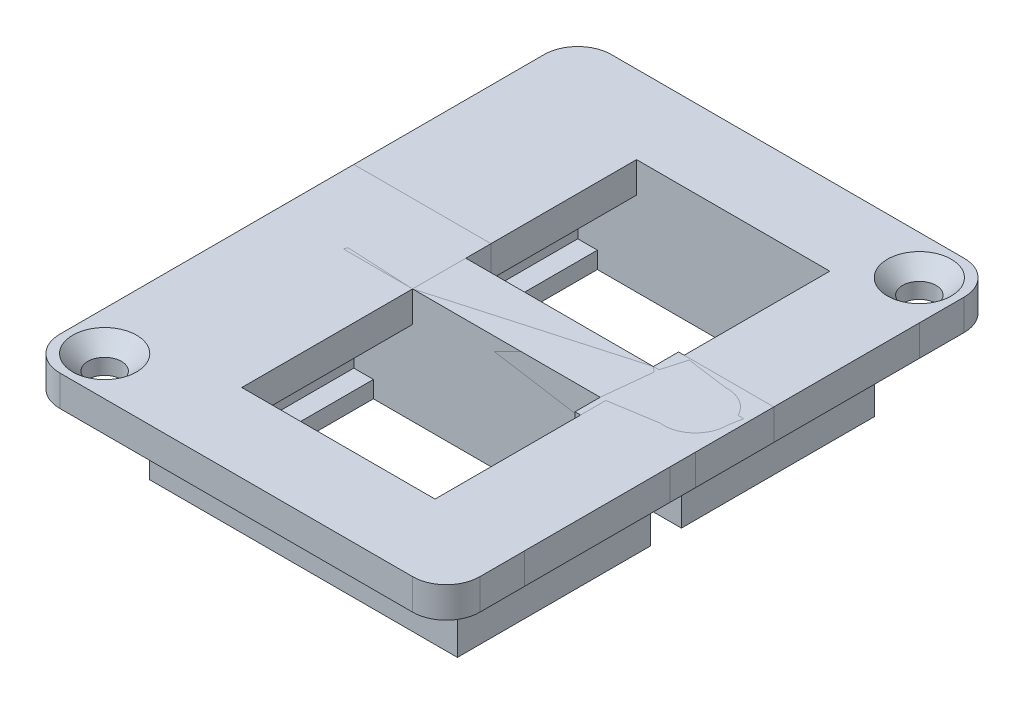
SolidWorks part; units mm, degrees
ref_plane "Front Plane" through (0, 0, 0) normal (0, 0, 1) x (1, 0, 0)
ref_plane "Top Plane" through (0, 0, 0) normal (0, 1, 0) x (1, 0, 0)
ref_plane "Right Plane" through (0, 0, 0) normal (1, 0, 0) x (0, 0, -1)
sketch "Sketch1" plane through (0, 0, 0) normal (0, 0, 1) x (1, 0, 0)
  line L0 (-5.75, 0) -> (10.25, 0) construction
  line L1 (10.25, 0) -> (10.25, -6.5) construction
  line L2 (10.25, -8) -> (11.75, -8) construction
  line L3 (-10.25, -10) -> (-10.25, -13.8781) construction
  line L4 (11.75, -8) -> (10.25, -6.5) construction
  line L5 (10.25, -8) -> (10.25, -9.5)
  line L6 (10.25, -10) -> (-5.75, -10) construction
  line L7 (-8.75, -8) -> (-8.75, -13.8781) construction
  line L8 (-5.75, 0) -> (-5.75, -10) construction
  line L9 (-5.75, 0) -> (-5.75, -8) construction
  line L10 (10.25, 0) -> (10.25, -8) construction
  line L11 (-10.25, -5) -> (-8.75, -8) construction
  line L12 (-10.25, -5) -> (-11.25, -8) construction
  line L13 (-11.75, -8) -> (-10, -8)
  line L14 (-8.75, -5) -> (-8.75, -10) construction
  line L15 (-10.25, -5) -> (-10.25, -10) construction
  line L16 (-8.75, -13.8781) -> (-10.25, -13.8781) construction
  line L19 (10.7534, 0.75) -> (10.7534, -1.9966)
  line L22 (10.25, -8) -> (11.75, -8)
  line L23 (11.75, -8) -> (11.75, -1.9966)
  line L27 (13.75, -1.9966) -> (18.75, -1.9966)
  line L33 (2.25, 0) -> (2.25, -10) construction
  line L47 (-11.75, -8) -> (-11.75, -1.9966)
  line L51 (-13.75, -1.9966) -> (-13.75, -9.5)
  line L53 (-13.75, -1.9966) -> (-18.75, -1.9966)
  line L59 (13.75, -1.9966) -> (13.75, -9.5)
  line L60 (18.75, 0.75) -> (18.75, -1.9966)
  line L61 (-18.75, 0.75) -> (-18.75, -1.9966)
  line L64 (-6.5034, -1.9966) -> (-11.75, -1.9966)
  line L65 (10.7534, -1.9966) -> (11.75, -1.9966)
  line L69 (-10, -9.5) -> (-10, -8)
  line L70 (-13.75, -9.5) -> (-10, -9.5)
  line L71 (-11.75, -9.5) -> (-10, -9.5) construction
  line L72 (10.25, -9.5) -> (13.75, -9.5)
  line L73 (10.25, -9.5) -> (11.75, -9.5) construction
  line L74 (-6.5034, 0.75) -> (-6.5034, -1.9966)
  line L75 (-6.5034, 0.75) -> (-18.75, 0.75)
  line L76 (10.7534, 0.75) -> (18.75, 0.75)
  dimension "D1" = 27.5
  dimension "D2" = 5
  dimension "D3" = 1.5
  dimension "D4" = 16
  dimension "D5" = 1.5
  dimension "D6" = 6.5
  dimension "D7" = 10
  dimension "D8" = 5
extrude "Boss-Extrude1" add sketch "Sketch1" along normal blind 15.25
sketch "Sketch2" plane through (0, 0, 15.25) normal (0, 0, 1) x (1, 0, 0)
  line L2 (18.7534, -1.9966) -> (-18.7534, -1.9966)
  line L4 (-18.7534, -1.9966) -> (-18.7534, 0.75)
  line L5 (18.7534, 0.75) -> (18.7534, -1.9966)
  line L7 (-18.7534, 0.75) -> (18.7534, 0.75)
extrude "Boss-Extrude2" add sketch "Sketch2" along normal blind 7
sketch "Sketch3" plane through (0, 0, 0) normal (0, 0, -1) x (-1, 0, 0)
  line L2 (18.7534, -1.9966) -> (-18.7534, -1.9966)
  line L4 (-18.7534, -1.9966) -> (-18.7534, 0.75)
  line L5 (18.7534, 0.75) -> (18.7534, -1.9966)
  line L7 (-18.7534, 0.75) -> (18.7534, 0.75)
extrude "Boss-Extrude3" add sketch "Sketch3" along normal blind 7
sketch "Sketch9" plane through (0, -1.9966, 0) normal (0, -1, 0) x (1, 0, 0)
  line L0 (18.75, 15.25) -> (18.75, 0) construction
  line L1 (18.7534, -7) -> (-18.7534, -7) construction
  line L2 (-18.75, 15.25) -> (-18.75, 0) construction
  line L3 (-18.7534, 22.25) -> (18.7534, 22.25) construction
  circle A1 centre (-15.25, 18.75) radius 1.5
  circle A5 centre (15.25, -3.5) radius 1.5
  dimension "D1" = 3.5
  dimension "D3" = 3.5
  dimension "D2" = 3.5
  dimension "D4" = 3.5
extrude "Cut-Extrude1" cut sketch "Sketch9" against normal blind 12
sketch "Sketch10" plane through (0, 0.75, 0) normal (0, 1, 0) x (1, 0, 0)
  circle A0 centre (-15.25, -18.75) radius 2.85
  circle A1 centre (15.25, 3.5) radius 2.85
extrude "Cut-Extrude2" cut sketch "Sketch10" against normal blind 6 draft 45
sketch "Sketch11" plane through (0, -1.9966, 0) normal (0, -1, 0) x (1, 0, 0)
  line L0 (-13.75, 15.25) -> (13.75, 15.25)
  line L21 (-13.75, 16.25) -> (13.75, 16.25)
  line L22 (-11.75, 16.25) -> (-6.2534, 16.25) construction
  line L25 (-11.75, 15.25) -> (-6.2534, 15.25) construction
  line L26 (-13.75, 15.25) -> (-13.75, 16.25)
  line L27 (13.75, 15.25) -> (13.75, 16.25)
  line L28 (13.75, 0) -> (13.75, -1)
  line L29 (-13.75, 0) -> (-13.75, -1)
  line L30 (-13.75, -1) -> (13.75, -1)
  line L31 (-13.75, 0) -> (13.75, 0)
extrude "Boss-Extrude5" add sketch "Sketch11" along normal up to vertex (7.5034 mm away) contours L21 L27 L0 L26 | L28 L30 L29 L31 up to point (-13.75, -9.5, 15.25)
ref_plane "Plane2" through (0, 0, -4) normal (0, 0, -1) x (-1, 0, 0)
pattern_linear "LPattern3" count 2 spacing 20 along (0, 0, -1) of "Boss-Extrude1"
fillet "Fillet1" radius 3 2 edges at (18.7534, -0.6233, 22.25) (-18.7534, -0.6233, 22.25)
fillet "Fillet2" radius 3 2 edges at (18.7534, -0.6233, -27) (-18.7534, -0.6233, -27)
sketch "Sketch13" plane through (0, -1.9966, 0) normal (0, -1, 0) x (1, 0, 0)
  line L0 (-6.5034, 7.625) -> (10.25, 7.625) construction
  line L1 (-6.5034, 15.25) -> (-6.5034, 0) construction
  line L2 (10.25, 15.25) -> (10.25, 0) construction
  line L3 (-6.5034, 15.25) -> (10.25, 15.25)
  line L4 (10.25, 15.25) -> (10.25, 0)
  line L5 (10.25, 0) -> (-6.5034, 0)
  line L6 (-6.5034, 15.25) -> (-6.5034, 0)
  line L7 (-6.5034, -20) -> (10.25, -20)
  line L8 (10.25, -20) -> (10.25, -4.75)
  line L9 (10.25, -4.75) -> (-6.5034, -4.75)
  line L10 (-6.5034, -4.75) -> (-6.5034, -20)
extrude "Cut-Extrude4" cut sketch "Sketch13" against normal blind 10
